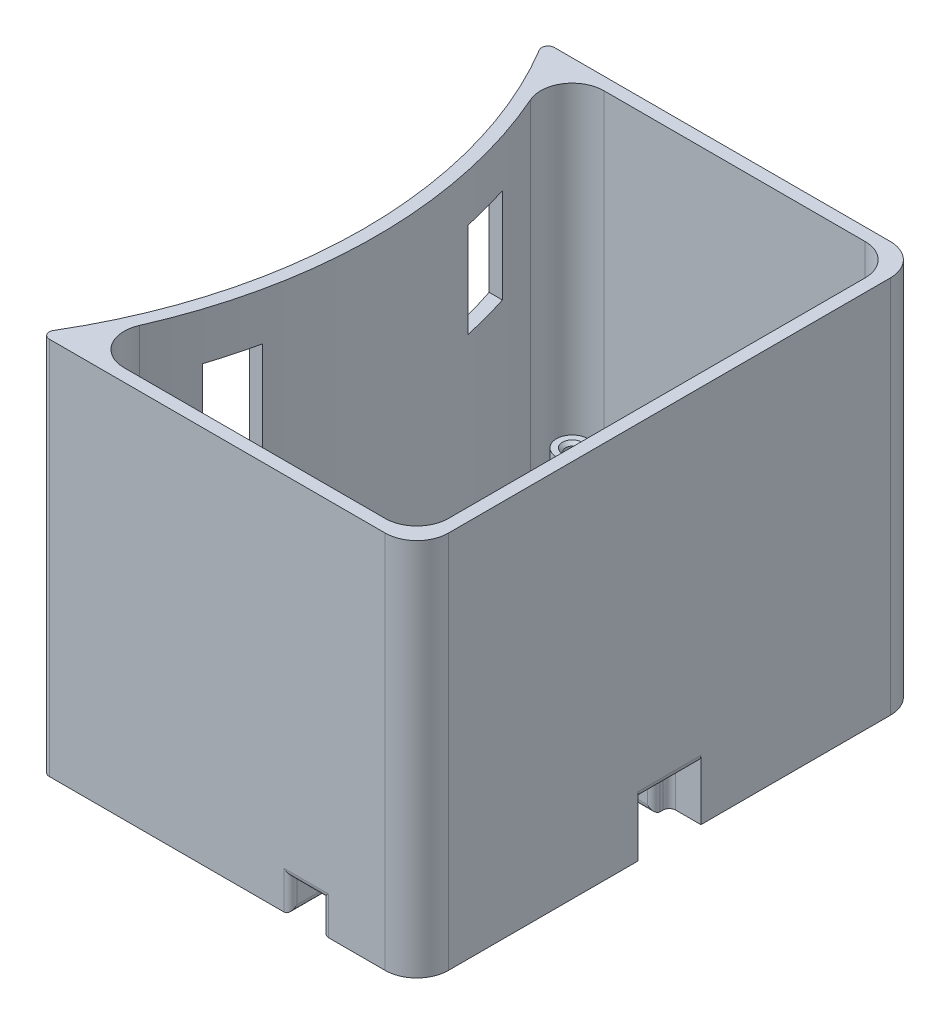
SolidWorks part; units mm, degrees
ref_plane "정면" through (0, 0, 0) normal (0, 0, 1) x (1, 0, 0)
ref_plane "윗면" through (0, 0, 0) normal (0, 1, 0) x (1, 0, 0)
ref_plane "우측면" through (0, 0, 0) normal (1, 0, 0) x (0, 0, -1)
sketch "스케치2" plane through (0, 0, 0) normal (0, 1, 0) x (1, 0, 0)
  line L1 (126.8858, -80) -> (246.8858, -80)
  line L2 (246.8858, -80) -> (246.8858, 80)
  line L3 (246.8858, 80) -> (126.8858, 80)
  circle A0 centre (0, 0) radius 150 construction
  arc A1 (126.8858, 80) -> (126.8858, -80) centre (0, 0) cw
  dimension "D1" = 300
  dimension "D2" = 160
  dimension "D3" = 120
  dimension "D4" = 80
extrude "보스-돌출1" add sketch "스케치2" along normal blind 120
shell "쉘1" thickness 4 removed face at (192.6643, 120, 0)
sketch "스케치4" plane through (0, 0, 0) normal (1, 0, 0) x (0, 0, -1)
  line L0 (0, -29.7637) -> (0, 207.892) construction
  line L1 (125.4294, 0) -> (-143.7989, 0) construction
  line L2 (122.7709, 90) -> (-152.772, 90) construction
  line L3 (47.5, 105) -> (32.5, 105)
  line L4 (-47.5, 75) -> (-32.5, 75)
  line L5 (-47.5, 75) -> (-47.5, 105)
  line L6 (-47.5, 105) -> (-32.5, 105)
  line L7 (-32.5, 75) -> (-32.5, 105)
  line L8 (-47.5, 75) -> (-32.5, 105) construction
  line L9 (-47.5, 105) -> (-32.5, 75) construction
  line L10 (32.5, 75) -> (32.5, 105)
  line L11 (47.5, 75) -> (32.5, 75)
  line L12 (47.5, 75) -> (47.5, 105)
  line L13 (47.5, 105) -> (32.5, 75) construction
  line L14 (47.5, 75) -> (32.5, 105) construction
  point P1 (-40, 90)
  point P16 (40, 90)
  dimension "D1" = 90
  dimension "D2" = 30
  dimension "D3" = 15
  dimension "D4" = 40
extrude "컷-돌출1" cut sketch "스케치4" along normal blind 154
sketch "스케치5" plane through (0, 4, 0) normal (0, 1, 0) x (1, 0, 0)
  line L3 (133.9403, -76) -> (242.8858, -76)
  line L4 (242.8858, -76) -> (242.8858, 76)
  line L5 (242.8858, 76) -> (133.9403, 76)
  line L6 (133.9403, -76) -> (242.8858, -76)
  line L7 (242.8858, -76) -> (242.8858, 76)
  line L8 (242.8858, 76) -> (133.9403, 76)
  arc A1 (133.9403, -76) -> (133.9403, 76) centre (0, 0) ccw
  arc A2 (133.9403, -76) -> (133.9403, 76) centre (0, 0) ccw
  dimension "D1" = 0
extrude "보스-돌출2" add sketch "스케치5" along normal blind 13
sketch "스케치6" plane through (0, 17, 0) normal (0, 1, 0) x (1, 0, 0)
  line L0 (114.227, 0) -> (345.777, 0) construction
  line L1 (246.8858, -80) -> (246.8858, 80) construction
  line L2 (236.8858, -10) -> (246.8858, -10)
  line L3 (236.8858, -10) -> (236.8858, 10)
  line L4 (236.8858, 10) -> (246.8858, 10)
  line L5 (246.8858, -10) -> (246.8858, 10)
  line L6 (236.8858, -10) -> (246.8858, 10) construction
  line L7 (236.8858, 10) -> (246.8858, -10) construction
  point P1 (241.8858, 0)
  dimension "D1" = 10
  dimension "D2" = 20
extrude "컷-돌출2" cut sketch "스케치6" against normal blind 17
sketch "스케치7" plane through (0, 0, 0) normal (0, -1, 0) x (1, 0, 0)
  line L0 (269.0023, 0) -> (246.8858, 0) construction
  line L1 (206.8858, -80) -> (216.8858, -80)
  line L4 (246.8858, 5) -> (226.8858, 5)
  line L5 (216.8858, 80) -> (216.8858, 15)
  line L7 (206.8858, 10) -> (206.8858, 80)
  line L8 (206.8858, 80) -> (216.8858, 80)
  line L9 (246.8858, -5) -> (246.8858, 5)
  line L10 (206.8858, -10) -> (206.8858, -80)
  line L11 (216.8858, -80) -> (216.8858, -15)
  line L12 (246.8858, -5) -> (226.8858, -5)
  line L13 (216.8858, 0) -> (101.682, 0) construction
  line L14 (126.8858, 80) -> (246.8858, 80) construction
  arc A0 (216.8858, 0) -> (206.8858, 10) centre (216.8858, 10) cw
  arc A1 (226.8858, 5) -> (216.8858, 15) centre (226.8858, 15) cw
  arc A2 (226.8858, -5) -> (216.8858, -15) centre (226.8858, -15) ccw
  arc A3 (216.8858, 0) -> (206.8858, -10) centre (216.8858, -10) ccw
  point P13 (213.8858, 0)
  dimension "D4" = 10
  dimension "D1" = 10
  dimension "D2" = 10
extrude "컷-돌출3" cut sketch "스케치7" against normal blind 10
fillet "필렛1" radius 10 6 edges at (246.8858, 60, -80) (246.8858, 60, 80) (242.8858, 68.5, -76) (242.8858, 68.5, 76) (133.9403, 68.5, 76) (133.9403, 68.5, -76)
sketch "스케치8" plane through (0, 0, 0) normal (0, -1, 0) x (1, 0, 0)
  line L0 (184.3009, 0) -> (126.8993, 0) construction
  line L1 (167.4773, 60) -> (137.4773, 60)
  line L2 (167.4773, -40) -> (144.5683, -40)
  line L3 (167.4773, -40) -> (167.4773, -60)
  line L4 (167.4773, -60) -> (137.4773, -60)
  line L6 (167.4773, 40) -> (167.4773, 60)
  line L7 (167.4773, 40) -> (144.5683, 40)
  arc A0 (126.8858, -80) -> (126.8858, 80) centre (0, 0) ccw construction
  arc A1 (137.4773, -60) -> (144.5683, -40) centre (0, 0) ccw
  arc A2 (137.4773, 60) -> (144.5683, 40) centre (0, 0) cw
  dimension "D1" = 20
  dimension "D2" = 40
  dimension "D3" = 30
extrude "컷-돌출4" cut sketch "스케치8" against normal blind 5
sketch "스케치9" plane through (0, 5, 0) normal (0, -1, 0) x (1, 0, 0)
  line L0 (137.2388, 0) -> (191.075, 0) construction
  line L1 (167.4773, -40) -> (144.5683, -40) construction
  line L3 (167.4773, -60) -> (167.4773, -40) construction
  circle A0 centre (157.4773, -50) radius 2.01
  circle A1 centre (157.4773, 50) radius 2.01
  dimension "D2" = 4.02
  dimension "D1" = 10
  dimension "D3" = 10
extrude "컷-돌출5" cut sketch "스케치9" against normal through all both and the other way through all
sketch "스케치10" plane through (0, 17, 0) normal (0, 1, 0) x (1, 0, 0)
  line L0 (206.0493, 0) -> (127.4341, 0) construction
  line L1 (140.1333, -120.4326) -> (140.1333, 123.5377) construction
  line L2 (242.8858, 112.8917) -> (242.8858, -112.0045) construction
  line L3 (242.8858, -66) -> (242.8858, -10) construction
  arc A0 (150.1333, 76) -> (140.9788, 61.9756) centre (150.1333, 66) ccw construction
  circle A1 centre (232.8858, 66) radius 5
  arc A2 (242.8858, 66) -> (232.8858, 76) centre (232.8858, 66) ccw construction
  circle A3 centre (150.1333, 66) radius 5
  arc A4 (150.1333, 76) -> (140.9788, 61.9756) centre (150.1333, 66) ccw construction
  circle A5 centre (150.1333, -66) radius 5
  circle A6 centre (232.8858, -66) radius 5
  dimension "D1" = 10
  dimension "D2" = 10
extrude "보스-돌출3" add sketch "스케치10" along normal blind 10
sketch "스케치11" plane through (0, 27, 0) normal (0, 1, 0) x (1, 0, 0)
  circle A2 centre (232.8858, 66) radius 2.1
  circle A3 centre (232.8858, 66) radius 2.1
  circle A4 centre (150.1333, -66) radius 2.1
  circle A5 centre (150.1333, 66) radius 2.1
  circle A6 centre (150.1333, 66) radius 2.1
  circle A7 centre (150.1333, -66) radius 2.1
  circle A9 centre (232.8858, -66) radius 2.1
  circle A10 centre (232.8858, -66) radius 2.1
  dimension "D2" = 2.9
  dimension "D1" = 2.9
  dimension "D3" = 2.9
  dimension "D4" = 2.9
extrude "컷-돌출6" cut sketch "스케치11" against normal through all both and the other way through all
fillet "필렛2" radius 2 25 edges at (239.8858, 17, 10) (239.8858, 17, -10) (231.8858, 0, 5) (219.8147, 0, 7.9289) (206.8858, 0, 45) (209.8147, 0, -2.9289) (231.8858, 0, -5) (219.8147, 0, -7.9289) (206.8858, 5, 80) (211.8858, 10, 80) (216.8858, 5, 80) (216.8858, 5, -80) (206.8858, 5, -80) (211.8858, 10, -80) (246.8858, 17, 0) (236.8858, 8.5, 10) (236.8858, 8.5, -10) (236.8858, 5, -5) (236.8858, 5, 5) (236.8858, 17, 0) (236.8858, 10, 0) (216.8858, 0, 47.5) (209.8147, 0, 2.9289) (206.8858, 0, -45) (216.8858, 0, -47.5)
chamfer "모따기1" distance 1 angle 45 8 edges at (157.4773, 17, -47.99) (157.4773, 17, 52.01) (157.4773, 5, -52.01) (157.4773, 5, 52.01) (232.8858, 27, -63.9) (232.8858, 27, 63.9) (150.1333, 27, 63.9) (150.1333, 27, -63.9)
chamfer "모따기2" distance 2 angle 45 4 edges at (232.8858, 17, 61) (232.8858, 17, -61) (150.1333, 17, -61) (150.1333, 17, 61)
fillet "필렛3" radius 2 2 edges at (126.8858, 60, 80) (126.8858, 60, -80)
